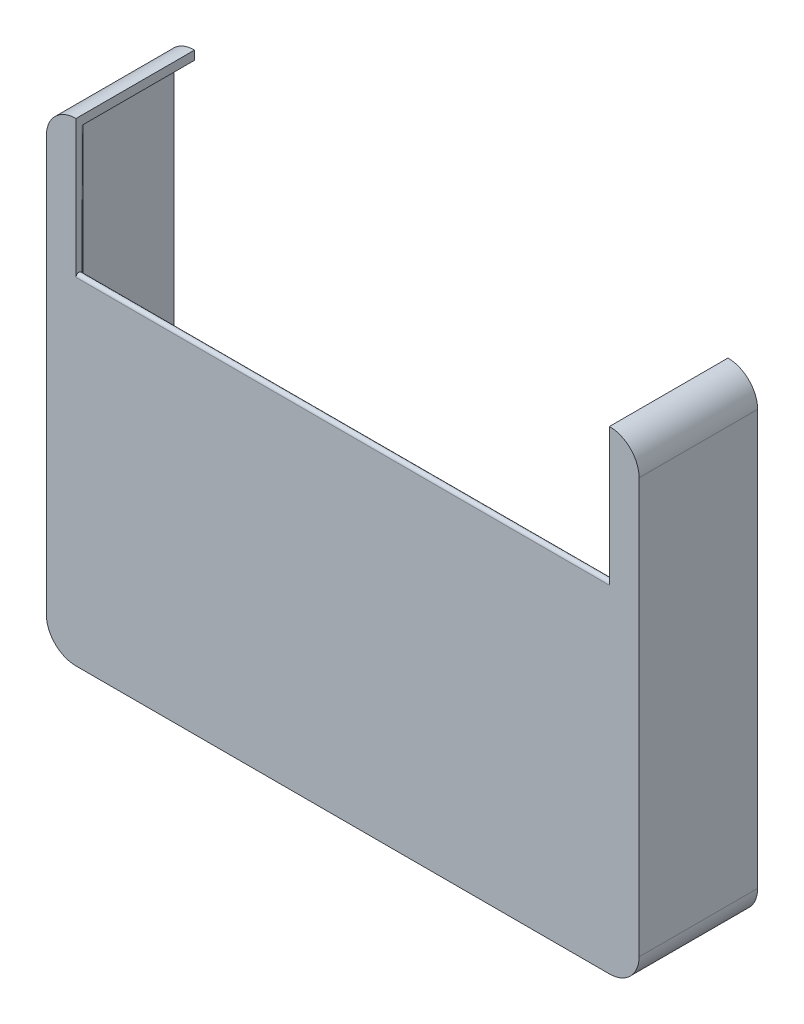
SolidWorks part; units mm, degrees
ref_plane "Plan de face" through (0, 0, 0) normal (0, 0, 1) x (1, 0, 0)
ref_plane "Plan de dessus" through (0, 0, 0) normal (0, 1, 0) x (1, 0, 0)
ref_plane "Plan de droite" through (0, 0, 0) normal (1, 0, 0) x (0, 0, -1)
sketch "Esquisse1" plane through (0, 0, 0) normal (0, 0, 1) x (1, 0, 0)
  line L1 (-50, 40) -> (50, 40)
  line L2 (-50, 40) -> (-50, -40)
  line L3 (-50, -40) -> (50, -40)
  line L4 (50, 40) -> (50, -40)
  line L5 (-50, 40) -> (50, -40) construction
  line L6 (-50, -40) -> (50, 40) construction
  point P0 (0, 0)
  dimension "D1" = 100
  dimension "D2" = 80
extrude "Boss.-Extru.1" add sketch "Esquisse1" along normal blind 20
shell "Coque1" thickness 1.5 removed face at (0, 0, 0)
fillet "Congé1" radius 5 4 edges at (-50, 40, 10) (50, 40, 10) (50, -40, 10) (-50, -40, 10)
sketch "Esquisse3" plane through (0, 40, 0) normal (0, 1, 0) x (1, 0, 0)
  line L4 (45, 0) -> (-45, 0)
  line L5 (-45, 0) -> (-45, -20)
  line L6 (-45, -20) -> (45, -20)
  line L7 (45, -20) -> (45, 0)
  line L8 (45, 0) -> (-45, 0)
  line L9 (-45, 0) -> (-45, -20)
  line L10 (-45, -20) -> (45, -20)
  line L11 (45, -20) -> (45, 0)
  dimension "D1" = 0
extrude "Enlèv. mat.-Extru.2" cut sketch "Esquisse3" against normal blind 20
fillet "Congé5" radius 20 1 edges at (0, 20, 18.5)
fillet "Congé6" radius 0.5 3 edges at (0, 20, 20) (45, 25.4503, 18.5) (-45, 25.4503, 18.5)
